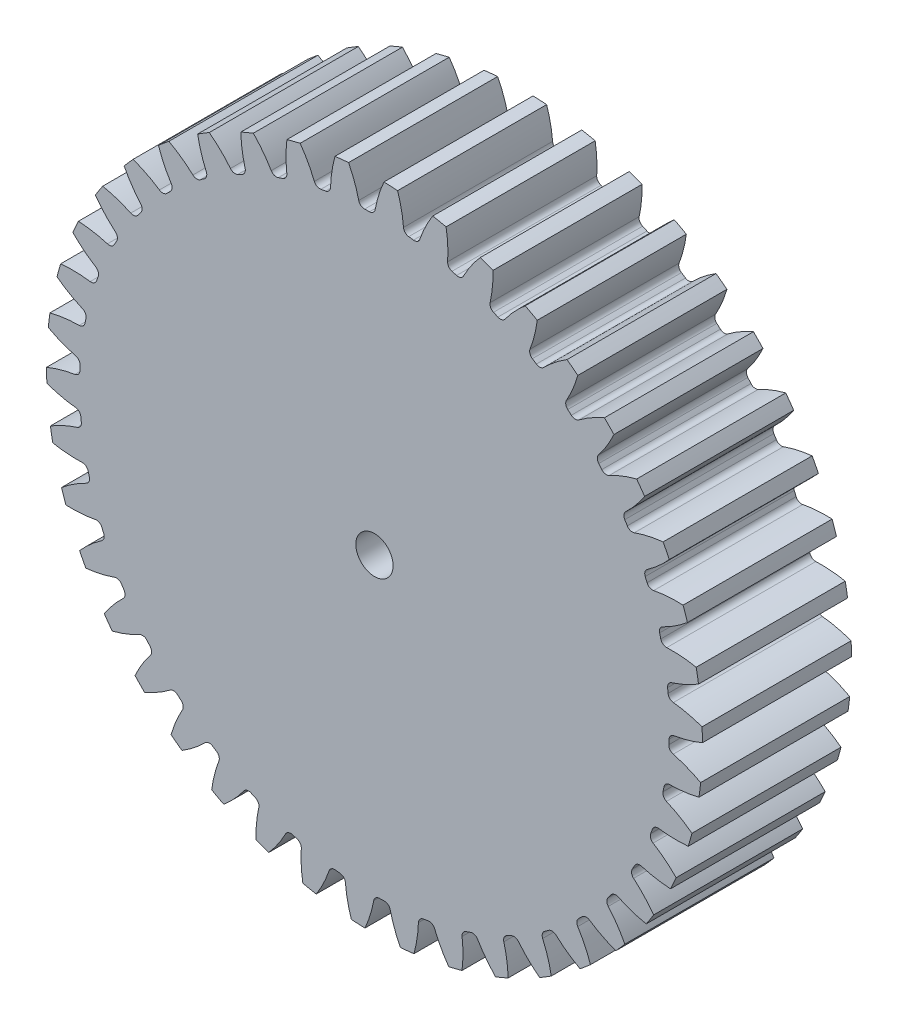
SolidWorks part; units mm, degrees
ref_plane "Front" through (0, 0, 0) normal (0, 0, 1) x (1, 0, 0)
ref_plane "Top" through (0, 0, 0) normal (0, 1, 0) x (1, 0, 0)
ref_plane "Right" through (0, 0, 0) normal (1, 0, 0) x (0, 0, -1)
sketch "Sketch3" plane through (0, 0, 0) normal (0, 0, 1) x (1, 0, 0)
  circle A0 centre (0, 0) radius 55.88
  dimension "od" = 111.76
extrude "gearBody" add sketch "Sketch3" along normal blind 25.4
sketch "Sketch2" plane through (0, 0, 0) normal (0, 0, 1) x (1, 0, 0)
  line L0 (0, 0) -> (47.7101, 19.7622) construction
  line L1 (64.0943, -14.273) -> (0, 0) construction
  line L2 (0, 0) -> (36.3143, 0) construction
  line L3 (53.3361, -0.6412) -> (53.1361, -4.6595) construction
  line L5 (53.2361, -2.6504) -> (0, 0) construction
  line L7 (0, 0) -> (51.641, 0) construction
  arc A0 (51.6306, -1.0364) -> (51.4782, -4.0969) centre (0, 0) ccw construction
  arc A1 (55.8795, 0.2375) -> (55.5796, -5.7865) centre (0, 0) ccw construction
  arc A2 (53.3361, -0.6412) -> (53.1361, -4.6595) centre (0, 0) ccw construction
  arc A3 (50.157, -2.9073) -> (50.1978, -2.0888) centre (0, 0) ccw
  arc A4 (64.0943, -14.273) -> (50.9039, -3.9369) centre (45.5113, -24.4032) ccw
  arc A5 (64.0943, -14.273) -> (65.1951, 7.8363) centre (0, 0) ccw
  arc A6 (65.1951, 7.8363) -> (51.0433, -1.1386) centre (47.7101, 19.7622) cw
  arc A7 (50.1978, -2.0888) -> (51.0433, -1.1386) centre (51.2015, -2.1306) cw
  arc A8 (50.9039, -3.9369) -> (50.157, -2.9073) centre (51.1599, -2.9655) cw
  point P6 (65.1951, 7.8363)
  point P22 (64.0943, -14.273)
  dimension "baseDia" = 103.282
  dimension "od" = 111.76
  dimension "pd" = 106.68
  dimension "rd" = 100.4824
  dimension "rFillet" = 1.0046
  dimension "pointX" = 65.1951
  dimension "pointY" = 7.8363
  dimension "CTT" = 4.0183
  dimension "flankCenterAngle" = 22.5
extrude "toothCut" cut sketch "Sketch2" along normal through all
pattern_circular "CirPattern1" count 42 over 360 about axis through (0, 0, 25.4) along (0, 0, -1) of "toothCut"
ref_axis "toothSpace" through (0, 0, 0) along (0.9988, -0.0497, 0)
ref_axis "Axis2" through (55.4472, -6.9415, 0) along (-0.9923, 0.1242, 0)
sketch "hub1Dia" plane through (0, 0, 0) normal (0, 0, -1) x (-1, 0, 0)
  circle A0 centre (0, 0) radius 12.7
  dimension "hub1Dia" = 25.4
sketch "hub2Dia" plane through (0, 0, 25.4) normal (0, 0, 1) x (1, 0, 0)
  circle A0 centre (0, 0) radius 12.7
  dimension "hub2dia" = 25.4
sketch "boreDia" plane through (0, 0, 0) normal (0, 0, 1) x (1, 0, 0)
  circle A0 centre (0, 0) radius 3.175
  dimension "boreDia" = 6.35
extrude "bore" cut sketch "boreDia" against normal mid plane 25400
sketch "kwy1sketch" plane through (0, 0, 0) normal (0, 0, 1) x (1, 0, 0)
  line L0 (-5.3365, 0.5333) -> (0, 0) construction
  line L1 (29.6963, 9.7954) -> (27.1704, -15.4787)
  line L2 (27.1704, -15.4787) -> (-4.4222, -12.3213)
  line L3 (29.6963, 9.7954) -> (-1.8963, 12.9528)
  line L4 (-4.4222, -12.3213) -> (0, 0)
  line L5 (0, 0) -> (-1.8963, 12.9528)
  line L6 (0, 0) -> (50.1791, -2.4982) construction
  line L7 (28.4334, -2.8417) -> (0, 0) construction
  arc A7 (50.157, -2.9073) -> (50.1978, -2.0888) centre (0, 0) ccw construction
  point P9 (28.4334, -2.8417)
  point P13 (-0.8902, 0.089)
  dimension "kwy1width" = 25.4
  dimension "kwy1depth" = 28.575
  dimension "kwy1angle" = 2.857
  dimension "kwy1Depth2" = 31.75
sketch "kwy2sketch" plane through (0, 0, 0) normal (0, 0, 1) x (1, 0, 0)
  line L0 (50.1791, -2.4982) -> (0, 0) construction
  line L1 (0, 0) -> (-2.8682, -2.347) construction
  line L2 (14.0721, 27.9248) -> (30.1575, 8.2673)
  line L3 (30.1575, 8.2673) -> (5.5855, -11.8395)
  line L4 (14.0721, 27.9248) -> (-10.4999, 7.8181)
  line L5 (5.5855, -11.8395) -> (0, 0)
  line L6 (0, 0) -> (-10.4999, 7.8181)
  arc A2 (50.157, -2.9073) -> (50.1978, -2.0888) centre (0, 0) ccw construction
  point P10 (22.1148, 18.0961)
  dimension "kwy2angle" = 42.143
  dimension "kwy2Width" = 25.4
  dimension "kwy2depth" = 28.575
  dimension "kwy2Depth2" = 31.75
sketch "kwy3sketch" plane through (0, 0, 0) normal (0, 0, 1) x (1, 0, 0)
  line L0 (50.1791, -2.4982) -> (0, 0) construction
  line L1 (0, 0) -> (-0.2666, -2.6679) construction
  line L2 (-9.7954, 29.6963) -> (15.4787, 27.1704)
  line L3 (15.4787, 27.1704) -> (12.3213, -4.4222)
  line L4 (-9.7954, 29.6963) -> (-12.9528, -1.8963)
  line L5 (12.3213, -4.4222) -> (0, 0)
  line L6 (-12.9528, -1.8963) -> (0, 0)
  point P10 (2.8417, 28.4334)
  dimension "kwy3angle" = 87.143
  dimension "kwy3depth" = 28.575
  dimension "kwy3width" = 25.4
  dimension "kwy3Depth2" = 31.75
sketch "kwy4sketch" plane through (0, 0, 0) normal (0, 0, 1) x (1, 0, 0)
  line L0 (50.1791, -2.4982) -> (0, 0) construction
  line L1 (0, 0) -> (1.3276, -1.6225) construction
  line L2 (-8.2673, 30.1575) -> (-27.9248, 14.0721)
  line L3 (-27.9248, 14.0721) -> (-7.8181, -10.4999)
  line L4 (-7.8181, -10.4999) -> (0, 0)
  line L5 (11.8395, 5.5855) -> (0, 0)
  line L6 (-8.2673, 30.1575) -> (11.8395, 5.5855)
  point P15 (-18.0961, 22.1148)
  dimension "kwy4angle" = 132.143
  dimension "kwy4depth" = 28.575
  dimension "kwy4width" = 25.4
  dimension "kwy4Depth2" = 31.75
sketch "kwy5sketch" plane through (0, 0, 0) normal (0, 0, 1) x (1, 0, 0)
  line L0 (50.1791, -2.4982) -> (0, 0) construction
  line L1 (0, 0) -> (1.7915, -0.179) construction
  line L2 (-27.1704, 15.4787) -> (-29.6963, -9.7954)
  line L3 (-29.6963, -9.7954) -> (1.8963, -12.9528)
  line L4 (-27.1704, 15.4787) -> (4.4222, 12.3213)
  line L5 (1.8963, -12.9528) -> (0, 0)
  line L6 (4.4222, 12.3213) -> (0, 0)
  point P10 (-28.4334, 2.8417)
  dimension "kwy5width" = 25.4
  dimension "kwy5depth" = 28.575
  dimension "kwy5angle" = 177.143
  dimension "kwy5Depth2" = 31.75
sketch "kwy6sketch" plane through (0, 0, 0) normal (0, 0, 1) x (1, 0, 0)
  line L0 (50.1791, -2.4982) -> (0, 0) construction
  line L1 (0, 0) -> (1.3923, 1.1393) construction
  line L2 (-30.1575, -8.2673) -> (-14.0721, -27.9248)
  line L3 (-14.0721, -27.9248) -> (10.4999, -7.8181)
  line L4 (-30.1575, -8.2673) -> (-5.5855, 11.8395)
  line L5 (10.4999, -7.8181) -> (0, 0)
  line L6 (-5.5855, 11.8395) -> (0, 0)
  point P10 (-22.1148, -18.0961)
  dimension "kwy6angle" = 222.143
  dimension "kwy6width" = 25.4
  dimension "kwy6depth" = 28.575
  dimension "kwy6Depth2" = 31.75
sketch "kwy7sketch" plane through (0, 0, 0) normal (0, 0, 1) x (1, 0, 0)
  line L0 (50.1791, -2.4982) -> (0, 0) construction
  line L1 (0, 0) -> (0.2004, 2.0055) construction
  line L2 (-15.4787, -27.1704) -> (9.7954, -29.6963)
  line L3 (-15.4787, -27.1704) -> (-12.3213, 4.4222)
  line L4 (9.7954, -29.6963) -> (12.9528, 1.8963)
  line L5 (-12.3213, 4.4222) -> (0, 0)
  line L6 (12.9528, 1.8963) -> (0, 0)
  point P10 (-2.8417, -28.4334)
  dimension "kwy7angle" = 87.143
  dimension "kwy7width" = 25.4
  dimension "kwy7depth" = 28.575
  dimension "kwy7angle1" = 267.143
  dimension "kwy7Depth2" = 31.75
sketch "kwy8sketch" plane through (0, 0, 0) normal (0, 0, 1) x (1, 0, 0)
  line L0 (50.1791, -2.4982) -> (0, 0) construction
  line L1 (0, 0) -> (-1.134, 1.3858) construction
  line L2 (8.2673, -30.1575) -> (27.9248, -14.0721)
  line L3 (27.9248, -14.0721) -> (7.8181, 10.4999)
  line L4 (8.2673, -30.1575) -> (-11.8395, -5.5855)
  line L5 (7.8181, 10.4999) -> (0, 0)
  line L6 (-11.8395, -5.5855) -> (0, 0)
  point P10 (18.0961, -22.1148)
  dimension "kwy8angle" = 312.143
  dimension "kwy8width" = 25.4
  dimension "kwy8depth" = 28.575
  dimension "kwy8Depth2" = 31.75
sketch "centerLine" plane through (0, 0, 0) normal (0, 1, 0) x (1, 0, 0)
  line L0 (0, 36.4807) -> (0, -59.6309) construction
ref_plane "CB1plane" through (0, 0, 0) normal (0, 0, -1) x (-1, 0, 0)
sketch "CB1diameter" plane through (0, 0, 0) normal (0, 0, -1) x (-1, 0, 0)
  circle A0 centre (0, 0) radius 12.7
  dimension "CB1diameter" = 25.4
ref_plane "CB2plane" through (0, 0, 25.4) normal (0, 0, 1) x (1, 0, 0)
sketch "CB2diameter" plane through (0, 0, 25.4) normal (0, 0, 1) x (1, 0, 0)
  circle A0 centre (0, 0) radius 12.7
  dimension "CB2diameter" = 25.4
ref_axis "Axis1" through (0, 0, 50) along (0, 0, -1)
sketch3d "3DSketch1" plane through (0, 0, 0) normal (0, 0, 1) x (1, 0, 0)
